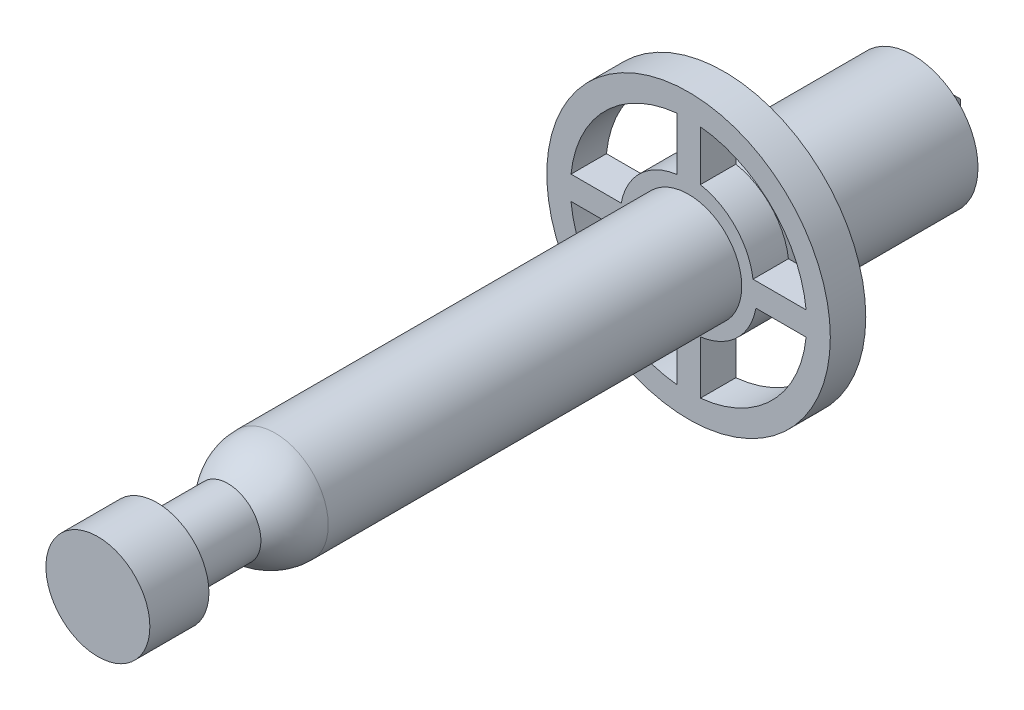
SolidWorks part; units mm, degrees
ref_plane "Front Plane" through (0, 0, 0) normal (0, 0, 1) x (1, 0, 0)
ref_plane "Top Plane" through (0, 0, 0) normal (0, 1, 0) x (1, 0, 0)
ref_plane "Right Plane" through (0, 0, 0) normal (1, 0, 0) x (0, 0, -1)
sketch "Sketch1" plane through (0, 0, 0) normal (0, 0, 1) x (1, 0, 0)
  circle A0 centre (0, -0.1473) radius 2.75
  dimension "D1" = 5.5
extrude "Boss-Extrude1" add sketch "Sketch1" along normal blind 8
sketch "Sketch4" plane through (0, 0, 0) normal (0, 1, 0) x (1, 0, 0)
  line L0 (0, 0) -> (0, 2)
  line L1 (0, 2) -> (-2, 0)
  line L2 (2.75, 0) -> (-2.75, 0) construction
  line L3 (-2, 0) -> (0, 0)
  dimension "D1" = 2
revolve "Revolve2" add sketch "Sketch4" angle 360 about L0
sketch "Sketch5" plane through (0, 0, 8) normal (0, 0, 1) x (1, 0, 0)
  circle A0 centre (0, 0) radius 2.25
  dimension "D1" = 4.5
extrude "Boss-Extrude2" add sketch "Sketch5" along normal blind 19
sketch "Sketch6" plane through (0, 0, 8) normal (0, 0, 1) x (1, 0, 0)
  circle A0 centre (0, 0) radius 6
  dimension "D1" = 12
extrude "Boss-Extrude4" add sketch "Sketch6" along normal blind 1.5
sketch "Sketch7" plane through (0, 0, 8) normal (0, 0, -1) x (-1, 0, 0)
  line L0 (0, 5) -> (0, 2.6027) construction
  line L1 (-5, 0) -> (-2.7461, 0) construction
  line L2 (-0.5, 4.9749) -> (-0.5, 2.5568)
  line L3 (0.5, 4.9749) -> (0.5, 2.5568)
  line L4 (-0.5, -2.8515) -> (-0.5, -4.9749)
  line L5 (0, -2.8973) -> (0, -5) construction
  line L6 (0.5, -2.8515) -> (0.5, -4.9749)
  line L7 (2.7461, 0) -> (5, 0) construction
  line L8 (-4.9749, -0.5) -> (-2.7273, -0.5)
  line L9 (-4.9749, 0.5) -> (-2.6727, 0.5)
  line L10 (2.7273, -0.5) -> (4.9749, -0.5)
  line L11 (2.6727, 0.5) -> (4.9749, 0.5)
  circle A0 centre (0, 0) radius 5
  circle A1 centre (0, 0) radius 6 construction
  circle A2 centre (0, -0.1473) radius 2.75 construction
  circle A3 centre (0, -0.1473) radius 2.75
  circle M9 centre (0, -0.1473) radius 2.75
  dimension "D1" = 1
  dimension "D2" = 0.5
  dimension "D3" = 0.5
extrude "Cut-Extrude1" cut sketch "Sketch7" against normal blind 1.5 contours L6 A0 L10 M9 region at (-2.6609, -2.6455, 8)
pattern_circular "CirPattern1" count 4 over 360 about axis through (0, 0, 8) along (0, 0, 1) of "Cut-Extrude1"
sketch "Sketch10" plane through (0, 0, 0) normal (1, 0, 0) x (0, 0, -1)
  line L0 (-27, 0) -> (-29, 0)
  line L1 (-27, 2.25) -> (-27, -2.25) construction
  line L2 (-29, 0) -> (-29, 1.4)
  line L3 (-27, 0) -> (-27, 2.25)
  line L4 (-9.5, 2.25) -> (-27, 2.25) construction
  spline S0 degree 2 poles (-29, 1.4) (-28.0866, 2.25) (-27, 2.25) knots 0 0 0 1 1 1
  dimension "D1" = 2
  dimension "D2" = 1.4
  dimension "D3" = 2.25
revolve "Revolve3" add sketch "Sketch10" angle 360 about L0
sketch "Sketch11" plane through (0, 0, 29) normal (0, 0, 1) x (1, 0, 0)
  circle A0 centre (0, 0) radius 1.4 construction
  circle A1 centre (0, 0) radius 1.4
extrude "Boss-Extrude5" add sketch "Sketch11" along normal blind 3
sketch "Sketch12" plane through (0, 0, 32) normal (0, 0, 1) x (1, 0, 0)
  circle A0 centre (0, 0) radius 2.2
  dimension "D1" = 4.4
extrude "Boss-Extrude6" add sketch "Sketch12" along normal blind 2.5
ref_axis "Axis1" through (0, 0, 75.4108) along (0, 0, -1)
